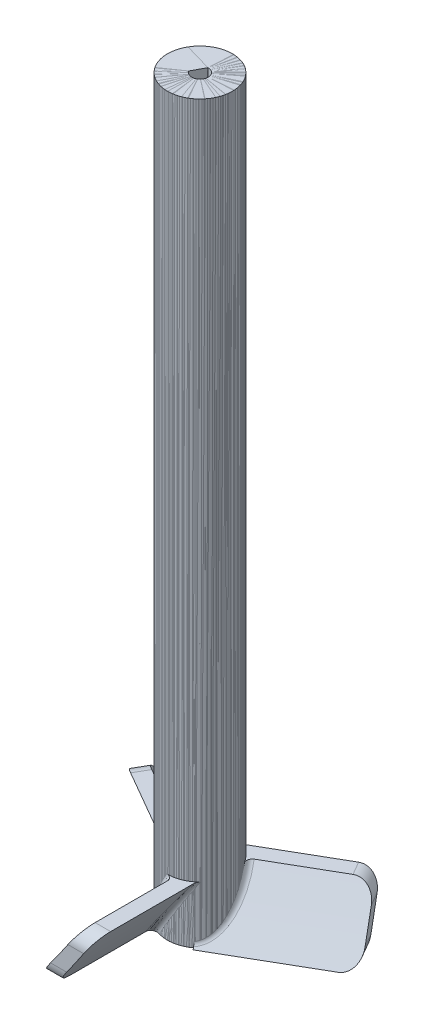
SolidWorks part; units mm, degrees
ref_plane "Front Plane" through (0, 0, 0) normal (0, 0, 1) x (1, 0, 0)
ref_plane "Top Plane" through (0, 0, 0) normal (0, 1, 0) x (1, 0, 0)
ref_plane "Right Plane" through (0, 0, 0) normal (1, 0, 0) x (0, 0, -1)
sketch "Sketch7" plane through (0, 0, 0) normal (0, 0, 1) x (1, 0, 0)
  line L0 (13.6726, 0) -> (-13.6726, 0) construction
  line L1 (6.849, 7) -> (4.9497, 7)
  line L2 (0, 0) -> (2, 0)
  arc A0 (0, 0) -> (4.9497, 7) centre (-91.3778, 69.8639) ccw
  arc A1 (6.849, 7) -> (2, 0) centre (-91.3778, 69.8639) cw
  dimension "D2" = 7
extrude "Boss-Extrude2" add sketch "Sketch7" along normal blind 15 contours A0 L1 A1 L2
fillet "Fillet1" radius 2 2 edges at (1, 0, 15) (5.8994, 7, 15)
sketch "Sketch10" plane through (0, 0, 0) normal (0, 1, 0) x (1, 0, 0)
  line L0 (0.3156, 0) -> (8.1957, 0) construction
  line L1 (4.9497, 0) -> (0, 0) construction
  line L2 (6.849, 0) -> (4.9497, 0) construction
  line L3 (2, 0) -> (6.849, 0) construction
  line L4 (4.2556, 0) -> (4.2556, 0.5251)
  line L5 (3.1481, -1000) -> (3.1481, 49000) construction
  circle A0 centre (4.2556, 0.5251) radius 3.9749
  point P5 (3.1481, 0)
  point P10 (-1.8519, 0)
  point P17 (3.1481, 0)
  dimension "D4" = 5
extrude "Boss-Extrude3" add sketch "Sketch10" along normal blind 90 contours A0 region at (0.3932, 0, -0.5251)
fillet "Fillet4" radius 0.7 2 edges at (1.2681, 1.6905, 2.0967) (3.7358, 2.3821, 3.4156)
pattern_circular "CirPattern1" count 3 over 360 about axis through (4.2556, 90, -0.5251) along (0, -1, 0) of bodies 103 102
sketch "Sketch11" plane through (0, 90, 0) normal (0, 1, 0) x (1, 0, 0)
  line L0 (3.4046, 0) -> (4.2264, 1.5247)
  arc A1 (3.4046, 0) -> (4.2264, 1.5247) centre (4.2556, 0.5251) ccw
  circle A2 centre (4.2556, 0.5251) radius 3.9749 construction
extrude "Cut-Extrude1" cut sketch "Sketch11" against normal blind 40 contours A1 L0
equation "\"insidebladediameter\"=0.01"
equation "\"height\"= 0.007"
equation "\"bladethickness\"=0.002"
equation "\"insidebladeradius\"= \"insidebladediameter\" / 2"
equation "\"D1@Sketch7\"=\"bladethickness\""
equation "\"D2@Sketch7\"=\"height\""
equation "\"bladewidth\"= \"height\" * cos ( \"bladeangle\" )"
equation "\"bladelength\"= 0.015"
equation "\"D1@Boss-Extrude2\"=\"bladelength\""
equation "\"bladetipradius\"= 0.002"
equation "\"D1@Fillet1\"=\"bladetipradius\""
equation "\"fusedistance\"= 0.0045"
equation "\"motorrodheight\"=0.09"
equation "\"D1@Boss-Extrude3\"=\"motorrodheight\""
equation "\"numberofblades\"= 3"
equation "\"D1@CirPattern1\"=\"numberofblades\""
equation "\"roddiameter\"= ( \"bladewidth\" + 0.003 )"
equation "\"roddepth\"= 0.005"
equation "\"bladeangle\"= 45deg"
equation "\"m\"=1"
equation "\"flatfacedist\"= 0.0005"
equation "\"motorshaftdiameter\"=0.002"
equation "\"D1@Sketch11\"=\"motorshaftdiameter\"/2"
equation "\"D3@Sketch7\"=\"bladewidth\""
equation "\"D2@Sketch10\"=\"roddiameter\"/2-\"fusedistance\""
equation "\"D1@Sketch10\"=\"roddiameter\""
equation "\"D2@Sketch11\"=\"flatfacedist\""
equation "\"bladefilletradius\"= 0.0007"
equation "\"D1@Fillet4\"=\"bladefilletradius\""
